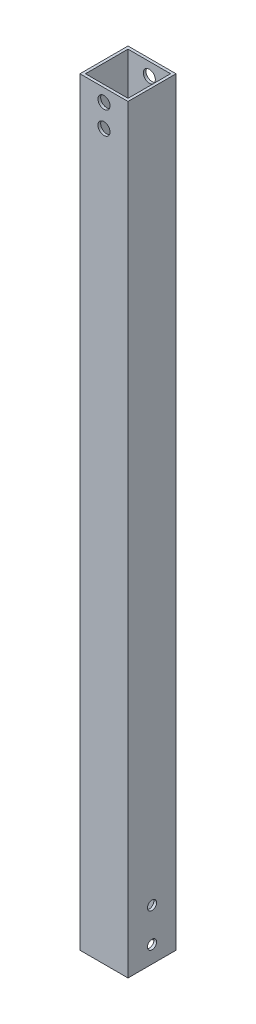
SolidWorks part; units mm, degrees
material "6061 Alloy"
ref_plane "Front Plane" through (0, 0, 0) normal (0, 0, 1) x (1, 0, 0)
ref_plane "Top Plane" through (0, 0, 0) normal (0, 1, 0) x (1, 0, 0)
ref_plane "Right Plane" through (0, 0, 0) normal (1, 0, 0) x (0, 0, -1)
sketch "Sketch1" plane through (0, 0, 0) normal (0, 1, 0) x (1, 0, 0)
  line L9 (12.7, -12.7) -> (-12.7, -12.7)
  line L10 (12.7, -12.7) -> (12.7, 12.7)
  line L11 (12.7, 12.7) -> (-12.7, 12.7)
  line L12 (-12.7, -12.7) -> (-12.7, 12.7)
  line L13 (12.7, -12.7) -> (-12.7, 12.7) construction
  line L14 (12.7, 12.7) -> (-12.7, -12.7) construction
  point P0 (0, 0)
  dimension "D1" = 25.4
extrude "Extrude-Thin1" add sketch "Sketch1" along normal blind 425.45 thin thin type mid plane wall 1.524
hole_wizard "1/4 Clearance Hole1" positions "Sketch2" profile "Sketch3" hole size "1/4" standard "ANSI Inch" end condition through all
sketch "Sketch2" plane through (0, 0, -13.462) normal (0, 0, -1) x (-1, 0, 0)
  point P0 (0, 418.2745)
  point P3 (0, 405.5745)
sketch "Sketch3" plane through (0, 418.2745, -13.462) normal (1, 0, 0) x (0, 1, 0)
  line L0 (0, 0) -> (0, 26.924)
  line L1 (0, 26.924) -> (3.3782, 26.924)
  line L2 (3.3782, 26.924) -> (3.3782, 0)
  line L5 (3.3782, 0) -> (0, 0)
  line L11 (0, -6.35) -> (0, 107.95) construction
  dimension "Thru Hole Dia." = 6.7564
  dimension "Thru Hole Depth" = 26.924
sketch "Sketch4" plane through (13.462, 0, 0) normal (1, 0, 0) x (0, 0, -1)
  line L0 (-13.462, 0) -> (13.462, 0) construction
  circle A0 centre (0, 9.525) radius 2.54
  circle A1 centre (0, 28.575) radius 2.54
  dimension "D1" = 5.08
  dimension "D2" = 9.525
  dimension "D3" = 28.575
hole_wizard "#10 Clearance Hole1" positions "Sketch5" profile "Sketch6" hole size "#10" standard "ANSI Inch" end condition through all
sketch "Sketch5" plane through (13.462, 0, 0) normal (1, 0, 0) x (0, 0, -1)
  point P0 (0, 9.525)
  point P3 (0, 28.575)
sketch "Sketch6" plane through (13.462, 9.525, 0) normal (0, 1, 0) x (0, 0, -1)
  line L0 (0, 0) -> (0, 26.924)
  line L1 (0, 26.924) -> (2.5527, 26.924)
  line L2 (2.5527, 26.924) -> (2.5527, 0)
  line L5 (2.5527, 0) -> (0, 0)
  line L11 (0, -6.35) -> (0, 107.95) construction
  dimension "Thru Hole Dia." = 5.1054
  dimension "Thru Hole Depth" = 26.924
